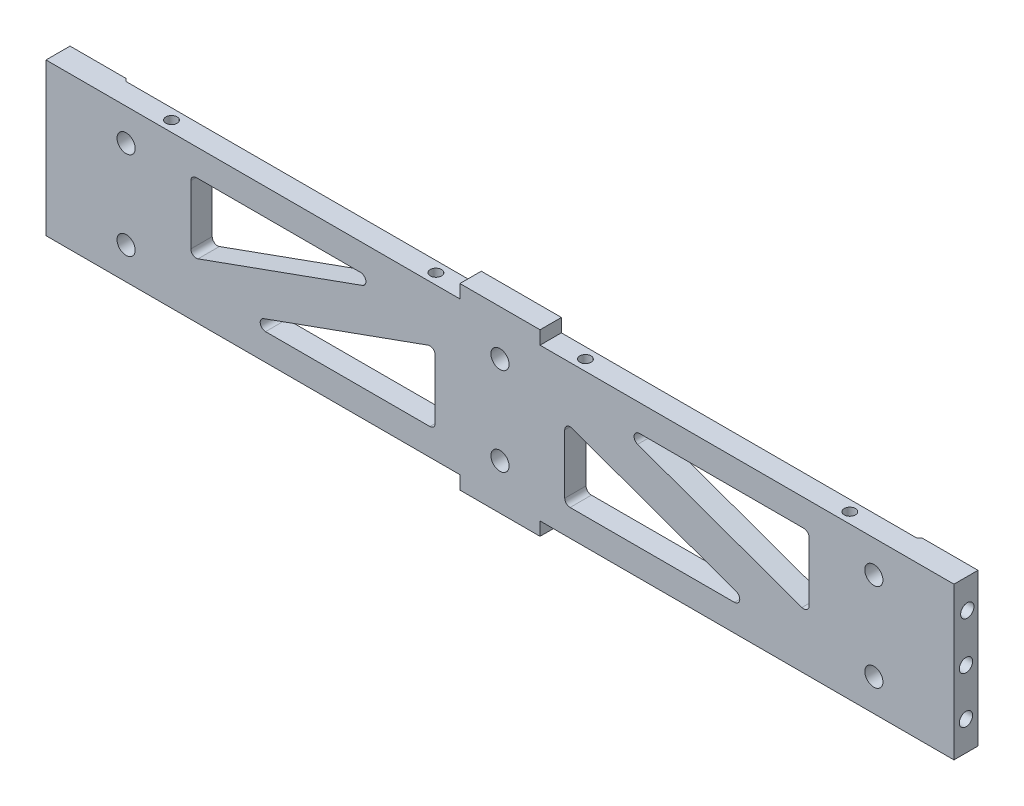
SolidWorks part; units mm, degrees
ref_plane "Plano frontal" through (0, 0, 0) normal (0, 0, 1) x (1, 0, 0)
ref_plane "Plano superior" through (0, 0, 0) normal (0, 1, 0) x (1, 0, 0)
ref_plane "Plano direito" through (0, 0, 0) normal (1, 0, 0) x (0, 0, -1)
sketch "Esboço1" plane through (0, 0, 0) normal (0, 0, 1) x (1, 0, 0)
  line L0 (185, 57) -> (185, 62)
  line L1 (0, 0) -> (155, 0)
  line L2 (0, 0) -> (0, 57)
  line L3 (0, 57) -> (155, 57)
  line L4 (340, 0) -> (340, 57)
  line L5 (185, 62) -> (155, 62)
  line L6 (155, 62) -> (155, 57)
  line L7 (185, 57) -> (340, 57)
  line L8 (185, 57) -> (340, 57) construction
  line L9 (155, 57) -> (0, 57) construction
  line L10 (185, 0) -> (340, 0)
  line L12 (155, 0) -> (155, -5)
  line L13 (155, -5) -> (185, -5)
  line L14 (185, 0) -> (185, -5)
  dimension "D1" = 57
  dimension "D2" = 340
  dimension "D3" = 30
  dimension "D4" = 5
  dimension "D5" = 5
extrude "Ressalto-extrusão1" add sketch "Esboço1" along normal blind 8
hole_wizard "Broca de rosquear para tarraxa de M82" positions "Esboço2" profile "Esboço3" hole size "M8" standard "ISO" end condition through all
sketch "Esboço2" plane through (0, 0, 8) normal (0, 0, 1) x (1, 0, 0)
  line L0 (0, 57) -> (0, 0) construction
  line L1 (340, 0) -> (340, 57) construction
  line L2 (155, 57) -> (0, 57) construction
  line L3 (0, 0) -> (155, 0) construction
  line L4 (170, 62) -> (170, -5) construction
  line L5 (185, 62) -> (155, 62) construction
  line L6 (155, -5) -> (185, -5) construction
  point P0 (30, 45)
  point P2 (30, 12)
  point P4 (170, 45)
  point P6 (170, 12)
  point P8 (310, 45)
  point P10 (310, 12)
  dimension "D1" = 30
  dimension "D2" = 30
  dimension "D3" = 30
  dimension "D4" = 12
  dimension "D5" = 30
  dimension "D6" = 12
  dimension "D9" = 12
  dimension "D10" = 12
  dimension "D11" = 12
  dimension "D12" = 12
sketch "Esboço3" plane through (30, 45, 8) normal (1, 0, 0) x (0, -1, 0)
  line L0 (0, 0) -> (0, 8)
  line L1 (0, 8) -> (3.4, 8)
  line L2 (3.4, 8) -> (3.4, 0)
  line L5 (3.4, 0) -> (0, 0)
  line L11 (0, -6.35) -> (0, 107.95) construction
  dimension "Thru Hole Dia." = 6.8
  dimension "Thru Hole Depth" = 8
sketch "Esboço8" plane through (0, 0, 0) normal (0, 0, -1) x (-1, 0, 0)
  line L1 (-340, 0) -> (-312, 0)
  line L2 (-340, 0) -> (-340, 57)
  line L3 (-340, 57) -> (-312, 57)
  line L4 (-312, 0) -> (-312, 57)
  line L5 (-155, 57) -> (0, 57) construction
  line L6 (0, 0) -> (-28, 0)
  line L7 (0, 0) -> (0, 57)
  line L8 (0, 57) -> (-28, 57)
  line L9 (-28, 0) -> (-28, 57)
  line L10 (-340, 0) -> (-340, 57) construction
  line L11 (-340, 57) -> (-185, 57) construction
  line L12 (-185, 0) -> (-340, 0) construction
  dimension "D1" = 28
  dimension "D2" = 28
extrude "Ressalto-extrusão2" add sketch "Esboço8" along normal blind 1
sketch "Esboço9" plane through (0, 0, 0) normal (0, 0, -1) x (-1, 0, 0)
  line L0 (-28, 0) -> (-155, 0) construction
  line L1 (-295, 0) -> (-185, 0)
  line L2 (-295, 0) -> (-295, 57)
  line L3 (-295, 57) -> (-185, 57)
  line L4 (-185, 0) -> (-185, 57)
  line L6 (-155, 57) -> (-45, 57)
  line L7 (-155, 57) -> (-155, 0)
  line L8 (-155, 0) -> (-45, 0)
  line L9 (-45, 57) -> (-45, 0)
  circle A0 centre (-310, 45) radius 3.4 construction
  circle A1 centre (-30, 45) radius 3.4 construction
  dimension "D1" = 15
  dimension "D2" = 15
hole_wizard "Broca de rosquear para tarraxa de M61" positions "Esboço6" profile "Esboço7" hole size "M6" standard "ISO"
sketch "Esboço6" plane through (340, 0, 0) normal (1, 0, 0) x (0, 0, -1)
  line L0 (-8, 57) -> (0, 57) construction
  line L1 (-8, 0) -> (0, 0) construction
  line L2 (-8, 0) -> (-8, 57) construction
  line L6 (-3.5, 0) -> (-3.5, 57) construction
  line L8 (-8, 57) -> (1, 57) construction
  line L9 (-8, 0) -> (1, 0) construction
  point P0 (-3, 46)
  point P2 (-3.5, 28.5)
  point P4 (-3.5, 11)
  dimension "D1" = 11
  dimension "D3" = 11
  dimension "D4" = 5
sketch "Esboço7" plane through (340, 46, 3) normal (0, 1, 0) x (0, 0, -1)
  line L0 (0, 0) -> (0, 16.5022)
  line L1 (0, 16.5022) -> (2.5, 15)
  line L2 (2.5, 15) -> (2.5, 0)
  line L5 (2.5, 0) -> (0, 0)
  line L10 (0, 16.5022) -> (-2.5, 15) construction
  line L11 (0, -6.35) -> (0, 107.95) construction
  dimension "Hole Dia." = 5
  dimension "Hole Depth" = 15
  dimension "Drill Angle" = 118
hole_wizard "Broca de rosquear para tarraxa de M62" positions "Esboço4" profile "Esboço5" hole size "M6" standard "ISO"
sketch "Esboço4" plane through (0, 0, 0) normal (-1, 0, 0) x (0, 0, 1)
  line L3 (3, 0) -> (3, 11) construction
  line L5 (3, 11) -> (3, 28.5) construction
  line L6 (3, 28.5) -> (3, 46) construction
  line L7 (3, 46) -> (3, 57) construction
  line L8 (8, 57) -> (8, 0) construction
  line L11 (8, 57) -> (-1, 57) construction
  line L12 (8, 0) -> (-1, 0) construction
  point P0 (3, 46)
  point P2 (3, 11)
  point P9 (3, 28.5)
  point P15 (3, 46)
  point P17 (3, 28.5)
  point P19 (3, 11)
  dimension "D1" = 5
  dimension "D2" = 11
  dimension "D3" = 11
sketch "Esboço5" plane through (0, 46, 3) normal (0, 1, 0) x (0, 0, 1)
  line L0 (0, 0) -> (0, 16.5022)
  line L1 (0, 16.5022) -> (2.5, 15)
  line L2 (2.5, 15) -> (2.5, 0)
  line L5 (2.5, 0) -> (0, 0)
  line L10 (0, 16.5022) -> (-2.5, 15) construction
  line L11 (0, -6.35) -> (0, 107.95) construction
  dimension "Hole Dia." = 5
  dimension "Hole Depth" = 15
  dimension "Drill Angle" = 118
chamfer "Chanfro2" distance 7 angle 45 1 edges at (28, 28.5, -1)
chamfer "Chanfro3" distance 7 angle 45 1 edges at (312, 28.5, -1)
sketch "Esboço10" plane through (0, 0, 0) normal (0, 0, -1) x (-1, 0, 0)
  line L6 (-285.7533, 47) -> (-210.7533, 47)
  line L8 (-210.7533, 47) -> (-285.7533, 20)
  line L9 (-285.7533, 20) -> (-285.7533, 47)
  line L10 (-269.2467, 10) -> (-194.2467, 37)
  line L11 (-194.2467, 37) -> (-194.2467, 10)
  line L12 (-194.2467, 10) -> (-269.2467, 10)
  line L14 (-318, 57) -> (-185, 57) construction
  line L15 (-185, 0) -> (-318, 0) construction
  line L16 (-145.7533, 10) -> (-70.7533, 10)
  line L17 (-310, 45) -> (-285.7533, 45) construction
  line L18 (-170, 12) -> (-194.2467, 12) construction
  line L19 (-170, 62) -> (-170, -5) construction
  line L20 (-185, 62) -> (-155, 62) construction
  line L21 (-155, -5) -> (-185, -5) construction
  line L42 (-145.7533, 37) -> (-145.7533, 10)
  line L43 (-70.7533, 10) -> (-145.7533, 37)
  line L44 (-54.2467, 20) -> (-54.2467, 47)
  line L45 (-129.2467, 47) -> (-54.2467, 20)
  line L46 (-54.2467, 47) -> (-129.2467, 47)
  dimension "D1" = 10
  dimension "D2" = 10
  dimension "D3" = 15
  dimension "D4" = 27
  dimension "D5" = 75
extrude "Corte-extrusão1" cut sketch "Esboço10" against normal blind 10
fillet "Filete1" radius 2 6 edges at (194.2467, 37, 4) (194.2467, 10, 4) (269.2467, 10, 4) (210.7533, 47, 4) (285.7533, 47, 4) (285.7533, 20, 4)
hole_wizard "Broca de rosquear para tarraxa de M51" positions "Esboço11" profile "Esboço12" hole size "M5" standard "ISO"
sketch "Esboço11" plane through (0, 57, 0) normal (0, 1, 0) x (1, 0, 0)
  line L0 (340, -4) -> (0, -4) construction
  line L1 (340, -8) -> (340, 1) construction
  line L2 (0, -8) -> (0, 1) construction
  line L5 (340, -8) -> (185, -8) construction
  line L6 (155, -8) -> (155, 0) construction
  line L7 (185, -8) -> (185, 0) construction
  point P0 (43, -4)
  point P2 (142, -4)
  point P4 (198, -4)
  point P6 (297, -4)
  dimension "D1" = 4
  dimension "D2" = 43
  dimension "D3" = 43
  dimension "D4" = 13
  dimension "D5" = 13
sketch "Esboço12" plane through (43, 57, 4) normal (1, 0, 0) x (0, 0, 1)
  line L0 (0, 0) -> (0, 16.2618)
  line L1 (0, 16.2618) -> (2.1, 15)
  line L2 (2.1, 15) -> (2.1, 0)
  line L5 (2.1, 0) -> (0, 0)
  line L10 (0, 16.2618) -> (-2.1, 15) construction
  line L11 (0, -6.35) -> (0, 107.95) construction
  dimension "Hole Dia." = 4.2
  dimension "Hole Depth" = 15
  dimension "Drill Angle" = 118
hole_wizard "Broca de rosquear para tarraxa de M52" positions "Esboço13" profile "Esboço14" hole size "M5" standard "ISO"
sketch "Esboço13" plane through (0, 0, 0) normal (0, -1, 0) x (-1, 0, 0)
  line L0 (-340, -4) -> (0, -4) construction
  line L1 (-340, -8) -> (-340, 1) construction
  line L2 (0, -8) -> (0, 1) construction
  line L4 (-185, -8) -> (-185, 0) construction
  line L5 (-155, -8) -> (-155, 0) construction
  line L6 (-185, -8) -> (-340, -8) construction
  point P0 (-150, -4)
  point P2 (-190, -4)
  point P4 (-297, -4)
  point P6 (-43, -4)
  point P25 (-272, -4)
  point P27 (-68, -4)
  dimension "D1" = 43
  dimension "D2" = 43
  dimension "D3" = 5
  dimension "D4" = 5
  dimension "D5" = 4
  dimension "D6" = 25
  dimension "25" = 25
sketch "Esboço14" plane through (150, 0, 4) normal (1, 0, 0) x (0, 0, -1)
  line L0 (0, 0) -> (0, 16.2618)
  line L1 (0, 16.2618) -> (2.1, 15)
  line L2 (2.1, 15) -> (2.1, 0)
  line L5 (2.1, 0) -> (0, 0)
  line L10 (0, 16.2618) -> (-2.1, 15) construction
  line L11 (0, -6.35) -> (0, 107.95) construction
  dimension "Hole Dia." = 4.2
  dimension "Hole Depth" = 15
  dimension "Drill Angle" = 118
fillet "Filete2" radius 2 6 edges at (54.2467, 47, 4) (54.2467, 20, 4) (129.2467, 47, 4) (70.7533, 10, 4) (145.7533, 37, 4) (145.7533, 10, 4)
